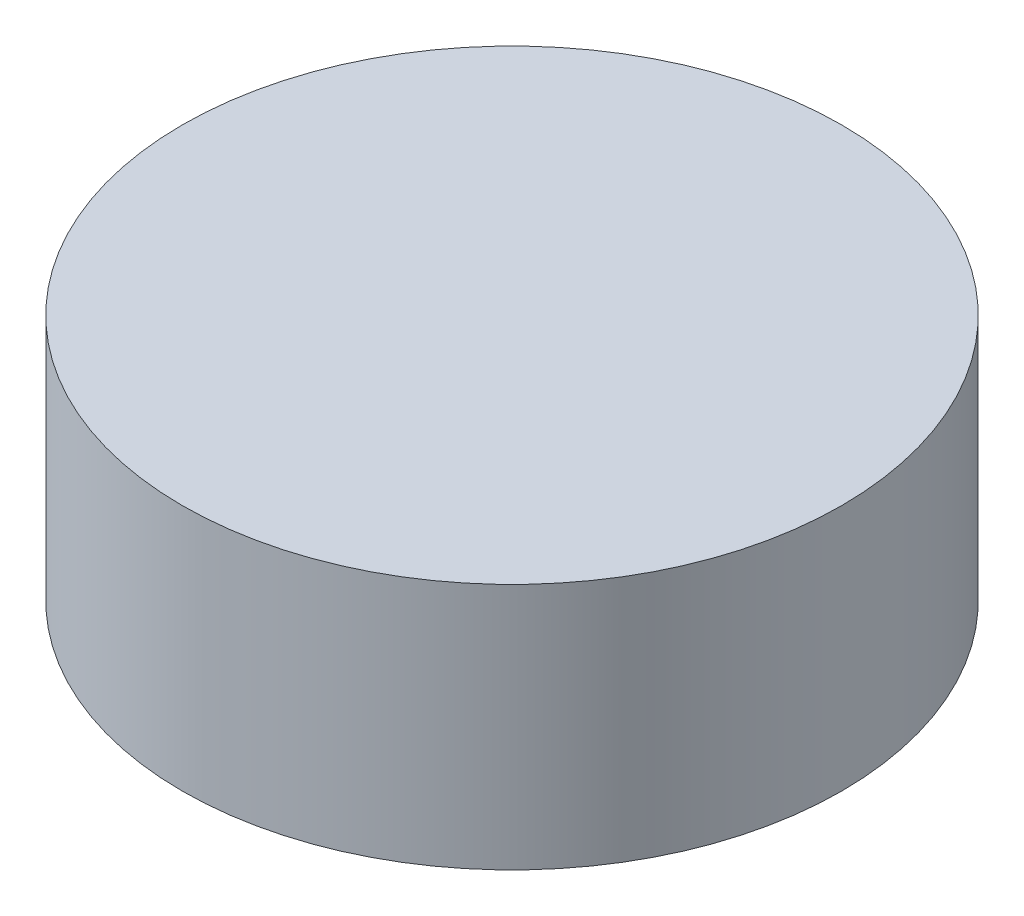
SolidWorks part; units mm, degrees
note: '?' marks a value the reader was unsure of.
ref_plane "Front Plane" through (0, 0, 0) normal (0, 0, 1) x (1, 0, 0)
ref_plane "Top Plane" through (0, 0, 0) normal (0, 1, 0) x (1, 0, 0)
ref_plane "Right Plane" through (0, 0, 0) normal (1, 0, 0) x (0, 0, -1)
sketch "Sketch2" plane through (0, 0, 0) normal (0, 1, 0) x (1, 0, 0)
  circle A0 centre (0, 0) radius 50.8
  dimension "D1" = 101.6
extrude "Boss-Extrude1" add sketch "Sketch2" along normal blind 38.1
sketch "Sketch4" plane through (0, 0, 0) normal (0, -1, 0) x (1, 0, 0)
  circle A0 centre (0, 0) radius 28.575 construction
  point P0 (0, 28.575)
  dimension "D1" = 57.15
hole_wizard "Fuel" positions "Sketch4" profile "Sketch6" hole size "#60" standard "ANSI Inch"
sketch "Sketch6" plane through (0, 0, 28.575) normal (1, 0, 0) x (0, 0, -1)
  line L0 (0, 0) -> (0, 25.7052)
  line L1 (0, 25.7052) -> (0.508, 25.4)
  line L2 (0.508, 25.4) -> (0.508, 0)
  line L5 (0.508, 0) -> (0, 0)
  line L10 (0, 25.7052) -> (-0.508, 25.4) construction
  line L11 (0, -6.35) -> (0, 107.95) construction
  dimension "Hole Dia." = 1.016
  dimension "Hole Depth" = 25.4
  dimension "Drill Angle" = 118
ref_axis "Axis1" through (0, 0, 55.88) along (0, 0, -1)?
ref_plane "Plane1" through (0, 0, 0) normal (-0.7071, 0.7071, 0) x (0, 0, -1)
sketch "Sketch8" plane through (0, 0, 0) normal (-0.7071, 0.7071, 0) x (0, 0, -1)
  ellipse E0 centre (-28.575, 0) end of major axis (-28.067, 0) minor radius 0.3592 construction
  point P0 (-28.575, 4.4901)
  point P1 (-28.575, 0)
  dimension "D1" = 4.4901
hole_wizard "#60 (0.04) Diameter Hole2" positions "Sketch8" profile "Sketch10" hole size "#60" standard "ANSI Inch"
sketch "Sketch10" plane through (-3.175, -3.175, 28.575) normal (0, 0, 1) x (0.7071, 0.7071, 0)
  line L0 (0, 0) -> (0, 25.7052)
  line L1 (0, 25.7052) -> (0.508, 25.4)
  line L2 (0.508, 25.4) -> (0.508, 0)
  line L5 (0.508, 0) -> (0, 0)
  line L10 (0, 25.7052) -> (-0.508, 25.4) construction
  line L11 (0, -6.35) -> (0, 107.95) construction
  dimension "Hole Dia." = 1.016
  dimension "Hole Depth" = 25.4
  dimension "Drill Angle" = 118
mirror "Mirror1" about plane through (0, 0, 0) normal (1, 0, 0) of "#60 (0.04) Diameter Hole2"
pattern_circular "CirPattern1" count 8 over 360 about axis through (0, 0, 0) along (0, 1, 0) of "Mirror1", "Fuel", "#60 (0.04) Diameter Hole2"
sketch "Sketch11" plane through (0, 0, 0) normal (1, 0, 0) x (0, 0, -1)
  line L1 (-49.53, 18.415) -> (-31.75, 18.415)
  line L2 (-49.53, 18.415) -> (-49.53, 12.065)
  line L3 (-49.53, 12.065) -> (-31.75, 12.065)
  line L4 (-31.75, 18.415) -> (-31.75, 12.065)
  line L5 (-50.8, 0) -> (50.8, 0) construction
  line L6 (0, 0) -> (0, 38.2919) construction
  line L7 (-50.8, 38.1) -> (-50.8, 0) construction
  line L8 (-31.75, 27.8233) -> (0, 27.8233)
  line L9 (-31.75, 27.8233) -> (-31.75, 22.7433)
  line L10 (-31.75, 22.7433) -> (0, 22.7433)
  line L11 (0, 27.8233) -> (0, 22.7433)
  point P4 (-49.283, 12.065)
  point P8 (-49.53, 15.24)
  dimension "D1" = 15.24
  dimension "D2" = 6.35
  dimension "D3" = 17.78
  dimension "D4" = 5.08
  dimension "D5" = 31.75
  dimension "D6" = 22.7433
  dimension "D7" = 1.27
revolve "Cut-Revolve1" cut sketch "Sketch11" angle 360 about L6
equation "\"D1@Sketch8\"=0.25*sin(45deg)"
